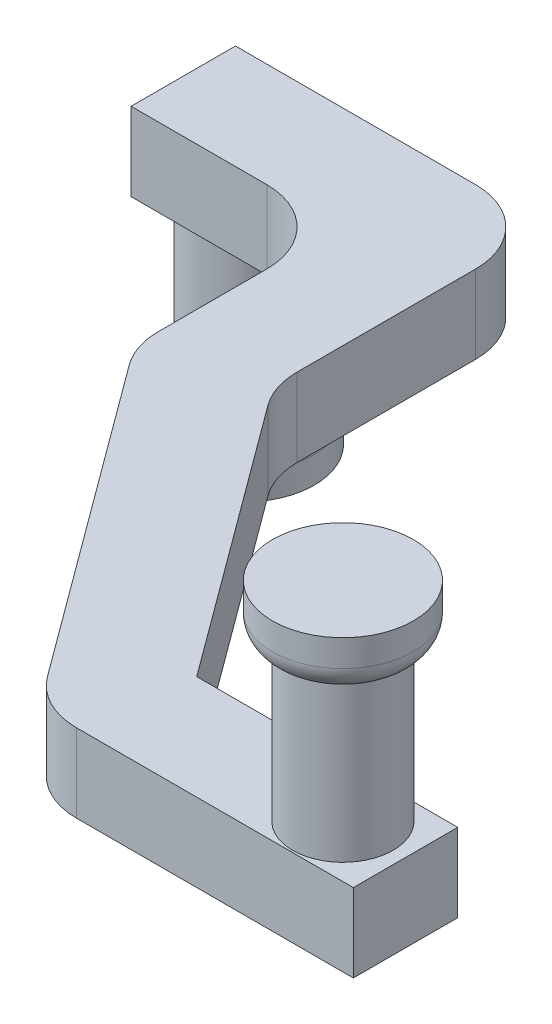
SolidWorks part; units mm, degrees
ref_plane "Front Plane" through (0, 0, 0) normal (0, 0, 1) x (1, 0, 0)
ref_plane "Top Plane" through (0, 0, 0) normal (0, 1, 0) x (1, 0, 0)
ref_plane "Right Plane" through (0, 0, 0) normal (1, 0, 0) x (0, 0, -1)
sketch "Sketch1" plane through (0, 0, 0) normal (0, 1, 0) x (1, 0, 0)
  line L0 (0, 0) -> (6, 0)
  line L1 (6, 0) -> (6, -5.2806)
  line L2 (6, -5.2806) -> (10.0922, -10.8346)
  line L3 (10.0922, -10.8346) -> (15.0922, -10.8346)
  line L4 (0, -2) -> (4, -2)
  line L5 (4, -2) -> (4, -5.9379)
  line L6 (4, -5.9379) -> (9.0816, -12.8346)
  line L7 (9.0816, -12.8346) -> (15.0922, -12.8346)
  line L8 (15.0922, -10.8346) -> (15.0922, -12.8346)
  line L9 (0, 0) -> (0, -2)
  point P11 (8, -8)
  point P12 (8, -8)
  point P13 (8, -7.8542)
  point P14 (8, -7.6427)
  point P15 (21.2987, -10.384)
  point P16 (8, -7.7399)
  point P17 (11.9404, -12.4107)
  point P18 (10.6684, -12.9557)
  point P19 (8, -7.0415)
  point P20 (10.0922, -10.8346)
  dimension "D1" = 6
  dimension "D4" = 5
  dimension "D5" = 2
extrude "Boss-Extrude1" add sketch "Sketch1" along normal blind 1.5
fillet "Fillet1" radius 1.4 5 edges at (6, 0.75, 5.2806) (4, 0.75, 5.9379) (4, 0.75, 2) (6, 0.75, 0) (9.0816, 0.75, 12.8346)
sketch "Sketch2" plane through (0, 1.5, 0) normal (0, 1, 0) x (1, 0, 0)
  line L0 (15.0922, -10.8346) -> (10.0922, -10.8346) construction
  line L1 (15.0922, -12.8346) -> (15.0922, -10.8346) construction
  circle A0 centre (13.8922, -11.8346) radius 0.9631
  point P4 (15.6718, -11.9557)
  dimension "D1" = 1
  dimension "D2" = 1.2
extrude "Boss-Extrude2" add sketch "Sketch2" along normal blind 3
sketch "Sketch3" plane through (0, 4.5, 0) normal (0, 1, 0) x (1, 0, 0)
  circle A0 centre (13.8922, -11.8346) radius 1.35
extrude "Boss-Extrude3" add sketch "Sketch3" along normal blind 1
fillet "Fillet2" radius 0.5 1 edges at (13.8922, 4.5, 13.1846)
sketch "Sketch4" plane through (0, 0, 0) normal (0, -1, 0) x (-1, 0, 0)
  circle A0 centre (-1.1759, -0.9924) radius 0.9631
  point P2 (-1.1759, -0.9924)
extrude "Boss-Extrude4" add sketch "Sketch4" along normal blind 3
sketch "Sketch5" plane through (0, -3, 0) normal (0, -1, 0) x (1, 0, 0)
  circle A0 centre (1.1927, 1.0322) radius 1.35
  point P3 (1.1927, 1.0322)
extrude "Boss-Extrude5" add sketch "Sketch5" along normal blind 1
fillet "Fillet3" radius 0.5 1 edges at (1.1927, -3, -0.3178)
